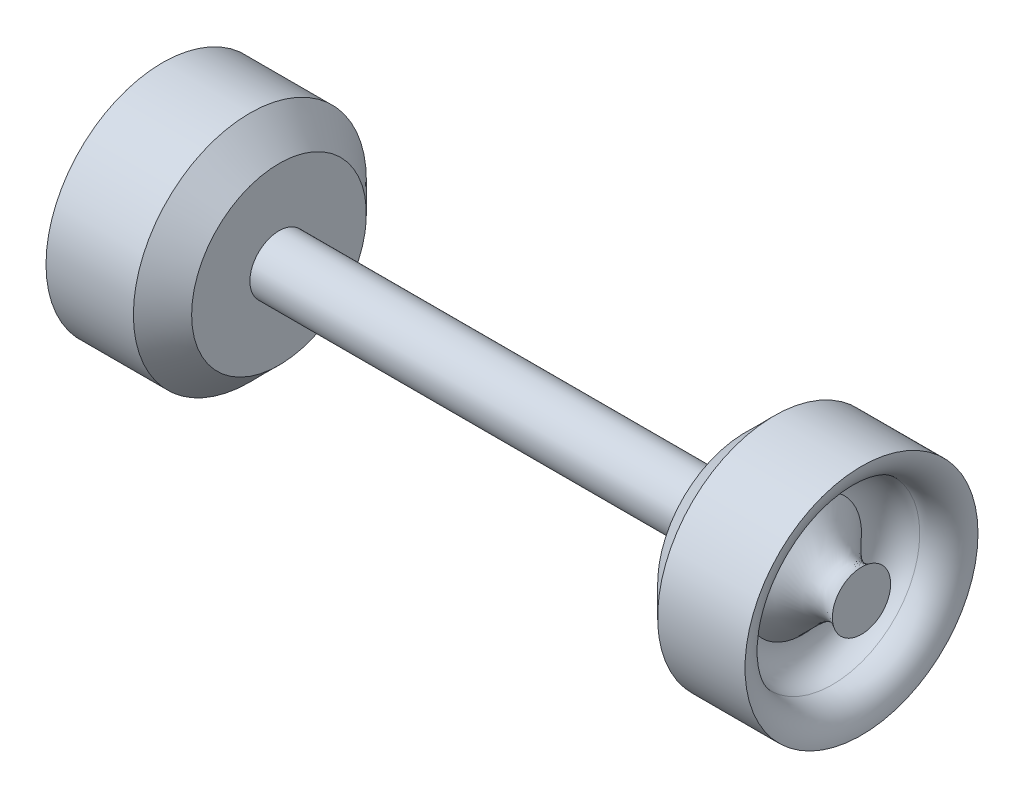
SolidWorks part; units mm, degrees
material "Cast Alloy Steel"
ref_plane "Front Plane" through (0, 0, 0) normal (0, 0, 1) x (1, 0, 0)
ref_plane "Top Plane" through (0, 0, 0) normal (0, 1, 0) x (1, 0, 0)
ref_plane "Right Plane" through (0, 0, 0) normal (1, 0, 0) x (0, 0, -1)
sketch "Sketch1" plane through (0, 0, 0) normal (1, 0, 0) x (0, 0, -1)
  circle A0 centre (0, 0) radius 2.5
  dimension "D1" = 5
extrude "Boss-Extrude1" add sketch "Sketch1" along normal blind 20
sketch "Sketch2" plane through (20, 0, 0) normal (1, 0, 0) x (0, 0, -1)
  circle A0 centre (0, 0) radius 10
  dimension "D1" = 20
extrude "Boss-Extrude2" add sketch "Sketch2" along normal blind 10
sketch "Sketch3" plane through (30, 0, 0) normal (1, 0, 0) x (0, 0, -1)
  circle A0 centre (0, 0) radius 7.5
  dimension "D1" = 15
extrude "Cut-Extrude1" cut sketch "Sketch3" against normal blind 5
sketch "Sketch5" plane through (25, 0, 0) normal (1, 0, 0) x (0, 0, -1)
  circle A0 centre (0, 0) radius 5
  dimension "D1" = 10
sketch "Sketch4" plane through (30, 0, 0) normal (1, 0, 0) x (0, 0, -1)
  circle A0 centre (0, 0) radius 2.5
  dimension "D1" = 5
loft "Loft1" add profiles "Sketch4", "Sketch5" connector at (30, 2.3392, 0.8822) connector at (25, 0.9184, -4.9149)
mirror "Mirror1" about plane through (0, 0, 0) normal (1, 0, 0) of "Boss-Extrude1", "Cut-Extrude1", "Boss-Extrude2", "Loft1"
fillet "Fillet1" radius 2.5 2 edges at (30, 0, -7.5) (25, 0, -7.5)
fillet "Fillet2" radius 2.5 2 edges at (-30, 0, -7.5) (-25, 0, -7.5)
chamfer "Chamfer1" distance 2.5 angle 45 2 edges at (-20, 0, -10) (20, 0, -10)
